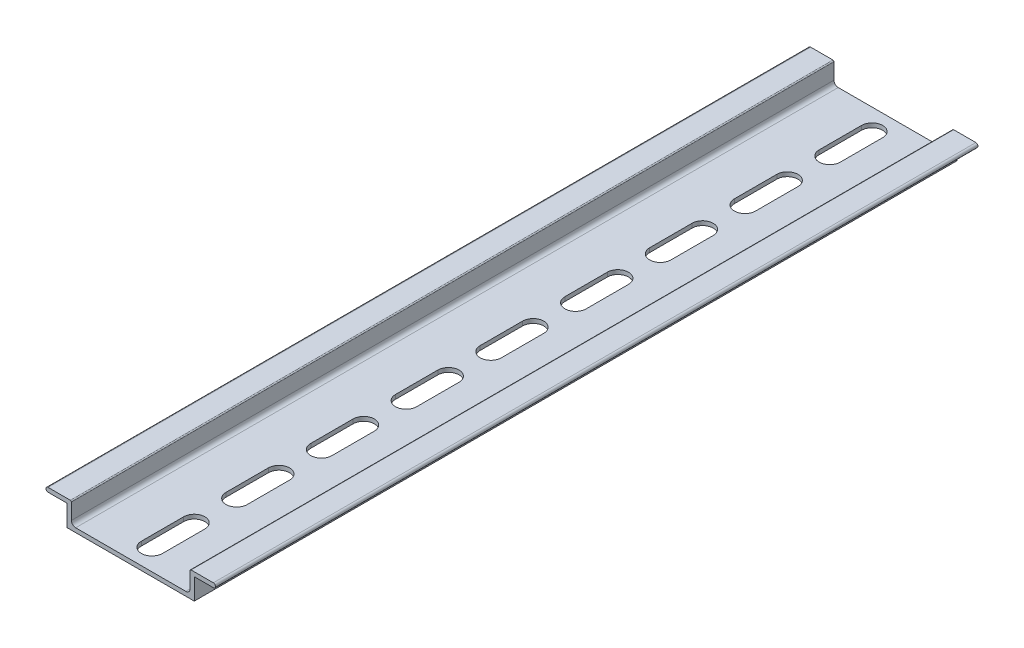
SolidWorks part; units mm, degrees
ref_plane "Front" through (0, 0, 0) normal (0, 0, 1) x (1, 0, 0)
ref_plane "Top" through (0, 0, 0) normal (0, 1, 0) x (1, 0, 0)
ref_plane "Right" through (0, 0, 0) normal (1, 0, 0) x (0, 0, -1)
sketch "Sketch1" plane through (0, 0, 0) normal (0, 0, 1) x (1, 0, 0)
  line L0 (-15, 0) -> (15, 0)
  line L1 (15, 0) -> (15, 5)
  line L2 (15, 5) -> (20, 5)
  line L3 (0, 0) -> (0, 7.8326) construction
  line L4 (-15, 5) -> (-20, 5)
  line L5 (-15, 0) -> (-15, 5)
  dimension "D1" = 30
  dimension "D2" = 5
  dimension "D3" = 5
extrude "Extrude-Thin1" add sketch "Sketch1" along normal mid plane 180 thin thin type one direction wall 1
fillet "Fillet1" radius 1 2 edges at (14, 1, 0) (-14, 1, 0)
fillet "Fillet2" radius 0.25 2 edges at (14, 6, 0) (-14, 6, 0)
fillet "Fillet3" 2 edges at (20, 6, 0) (20, 5, 0) type full round first side face at (17.125, 6, 0) second side face at (17.5, 5, 0) middle face at (20, 5.5, 0)
fillet "Fillet4" 2 edges at (-20, 6, 0) (-20, 5, 0) type full round first side face at (-17.125, 6, 0) second side face at (-17.5, 5, 0) middle face at (-20, 5.5, 0)
sketch "Sketch2" plane through (0, 1, 0) normal (0, 1, 0) x (1, 0, 0)
  line L0 (0, -5) -> (0, 5) construction
  line L1 (-2.5, -5) -> (-2.5, 5)
  line L2 (2.5, -5) -> (2.5, 5)
  arc A0 (-2.5, -5) -> (2.5, -5) centre (0, -5) ccw
  arc A1 (2.5, 5) -> (-2.5, 5) centre (0, 5) ccw
  point P2 (0, 0)
  dimension "D1" = 10
  dimension "D2" = 5
extrude "Cut-Extrude1" cut sketch "Sketch2" against normal through all
pattern_linear "LPattern1" count 5 spacing 20 along (0, 0, -1) count 5 spacing 20 along (0, 0, 1) of "Cut-Extrude1" pattern seed only yes
